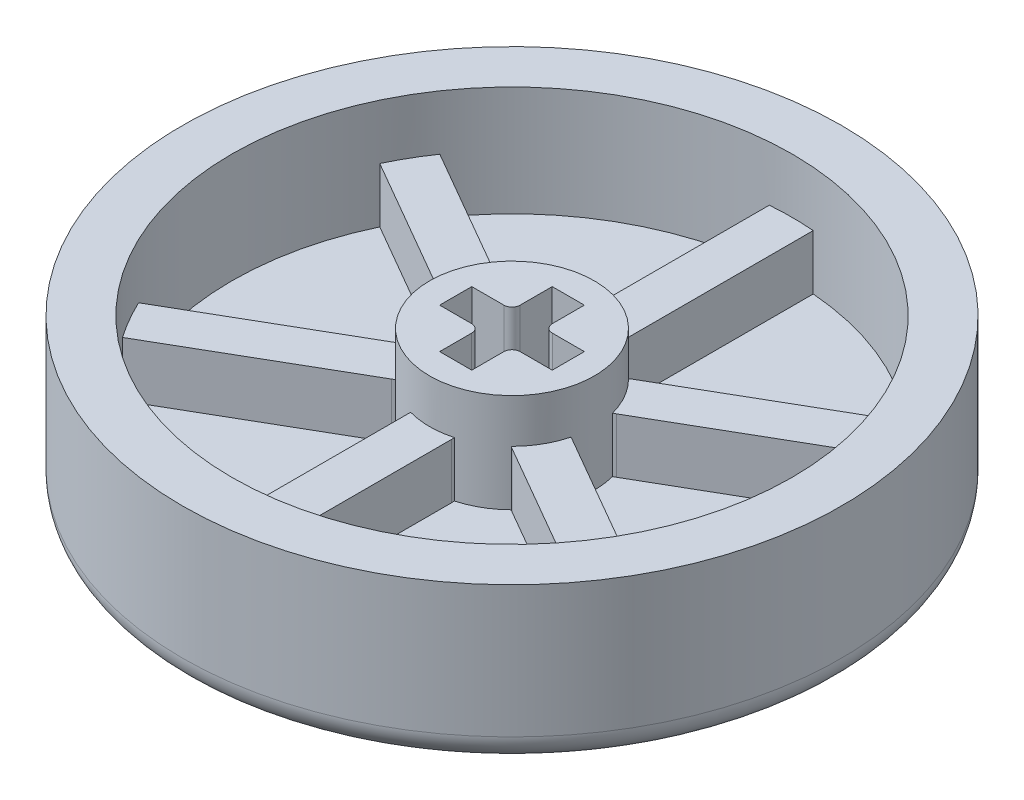
SolidWorks part; units mm, degrees
ref_plane "Front Plane" through (0, 0, 0) normal (0, 0, 1) x (1, 0, 0)
ref_plane "Top Plane" through (0, 0, 0) normal (0, 1, 0) x (1, 0, 0)
ref_plane "Right Plane" through (0, 0, 0) normal (1, 0, 0) x (0, 0, -1)
sketch "Sketch1" plane through (0, 0, 0) normal (0, 1, 0) x (1, 0, 0)
  circle A0 centre (0, 0) radius 12
  dimension "D1" = 24
extrude "button top" add sketch "Sketch1" along normal blind 1.8
sketch "Sketch2" plane through (0, 1.8, 0) normal (0, 1, 0) x (1, 0, 0)
  circle A3 centre (0, 0) radius 12
  circle A4 centre (0, 0) radius 12 construction
  circle A5 centre (0, 0) radius 10.2
  dimension "D1" = 1.8
extrude "button walls" add sketch "Sketch2" along normal blind 4
sketch "Sketch3" plane through (0, 1.8, 0) normal (0, 1, 0) x (1, 0, 0)
  line L0 (0, -2.05) -> (0, 2.05) construction
  line L1 (-2.05, 0) -> (2.05, 0) construction
  line L2 (-0.585, 0.885) -> (-0.585, 2.05)
  line L3 (-0.585, -2.05) -> (0.585, -2.05)
  line L4 (-0.585, -2.05) -> (-0.585, -0.885)
  line L5 (-0.585, 2.05) -> (0.585, 2.05)
  line L6 (0.585, -2.05) -> (0.585, -0.885)
  line L7 (-0.585, -2.05) -> (0.585, 2.05) construction
  line L8 (-0.585, 2.05) -> (0.585, -2.05) construction
  line L9 (-2.05, -0.585) -> (-0.885, -0.585)
  line L10 (-2.05, -0.585) -> (-2.05, 0.585)
  line L11 (-2.05, 0.585) -> (-0.885, 0.585)
  line L12 (2.05, -0.585) -> (2.05, 0.585)
  line L13 (-2.05, -0.585) -> (2.05, 0.585) construction
  line L14 (-2.05, 0.585) -> (2.05, -0.585) construction
  line L15 (0.885, 0.585) -> (2.05, 0.585)
  line L16 (0.585, 0.885) -> (0.585, 2.05)
  line L17 (0.885, -0.585) -> (2.05, -0.585)
  circle A0 centre (0, 0) radius 3
  arc A1 (-0.585, -0.885) -> (-0.885, -0.585) centre (-0.885, -0.885) ccw
  arc A2 (0.585, -0.885) -> (0.885, -0.585) centre (0.885, -0.885) cw
  arc A3 (0.885, 0.585) -> (0.585, 0.885) centre (0.885, 0.885) cw
  arc A4 (-0.585, 0.885) -> (-0.885, 0.585) centre (-0.885, 0.885) cw
  point P6 (0, 0)
  point P9 (0, 0)
  point P17 (0, 0)
  point P22 (2.05, 0)
  point P23 (0, 0)
  point P24 (0, 2.05)
  point P29 (0.585, -0.585)
  point P32 (0.585, 0.585)
  point P35 (0, 0)
  dimension "D1" = 6
  dimension "D4" = 0.3
  dimension "D2" = 4.1
  dimension "D3" = 1.17
extrude "stem housing" add sketch "Sketch3" along normal blind 3.6
sketch "Sketch4" plane through (0, 1.8, 0) normal (0, 1, 0) x (1, 0, 0)
  line L0 (0, 3) -> (0, 10.2) construction
  line L1 (-0.8, 3) -> (-0.8, 10.2)
  line L2 (0.8, 3) -> (0.8, 10.2)
  line L3 (2.5981, 1.5) -> (8.8335, 5.1) construction
  line L4 (2.1981, 2.1928) -> (8.4335, 5.7928)
  line L5 (2.9981, 0.8072) -> (9.2335, 4.4072)
  line L6 (2.5981, -1.5) -> (8.8335, -5.1) construction
  line L7 (2.9981, -0.8072) -> (9.2335, -4.4072)
  line L8 (2.1981, -2.1928) -> (8.4335, -5.7928)
  line L9 (0, -3) -> (0, -10.2) construction
  line L10 (0.8, -3) -> (0.8, -10.2)
  line L11 (-0.8, -3) -> (-0.8, -10.2)
  line L12 (-2.5981, -1.5) -> (-8.8335, -5.1) construction
  line L13 (-2.1981, -2.1928) -> (-8.4335, -5.7928)
  line L14 (-2.9981, -0.8072) -> (-9.2335, -4.4072)
  line L15 (-2.5981, 1.5) -> (-8.8335, 5.1) construction
  line L16 (-2.9981, 0.8072) -> (-9.2335, 4.4072)
  line L17 (-2.1981, 2.1928) -> (-8.4335, 5.7928)
  circle A0 centre (0, 0) radius 3 construction
  circle A1 centre (0, 0) radius 3 construction
  circle A2 centre (0, 0) radius 10.2 construction
  arc A3 (-0.8, 3) -> (0.8, 3) centre (0, 3) ccw
  arc A4 (0.8, 10.2) -> (-0.8, 10.2) centre (0, 10.2) ccw
  arc A5 (2.1981, 2.1928) -> (2.9981, 0.8072) centre (2.5981, 1.5) ccw
  arc A6 (9.2335, 4.4072) -> (8.4335, 5.7928) centre (8.8335, 5.1) ccw
  arc A7 (2.9981, -0.8072) -> (2.1981, -2.1928) centre (2.5981, -1.5) ccw
  arc A8 (8.4335, -5.7928) -> (9.2335, -4.4072) centre (8.8335, -5.1) ccw
  arc A9 (0.8, -3) -> (-0.8, -3) centre (0, -3) ccw
  arc A10 (-0.8, -10.2) -> (0.8, -10.2) centre (0, -10.2) ccw
  arc A11 (-2.1981, -2.1928) -> (-2.9981, -0.8072) centre (-2.5981, -1.5) ccw
  arc A12 (-9.2335, -4.4072) -> (-8.4335, -5.7928) centre (-8.8335, -5.1) ccw
  arc A13 (-2.9981, 0.8072) -> (-2.1981, 2.1928) centre (-2.5981, 1.5) ccw
  arc A14 (-8.4335, 5.7928) -> (-9.2335, 4.4072) centre (-8.8335, 5.1) ccw
  point P9 (0, 6.6)
  point P18 (5.7158, 3.3)
  point P25 (5.7158, -3.3)
  point P32 (0, -6.6)
  point P39 (-5.7158, -3.3)
  point P46 (-5.7158, 3.3)
  point P51 (0, 0)
  dimension "D1" = 1.6
  dimension "D2" = 6
extrude "Boss-Extrude4" add sketch "Sketch4" along normal blind 2
fillet "Fillet1" radius 1 1 edges at (0, 0, 12)
